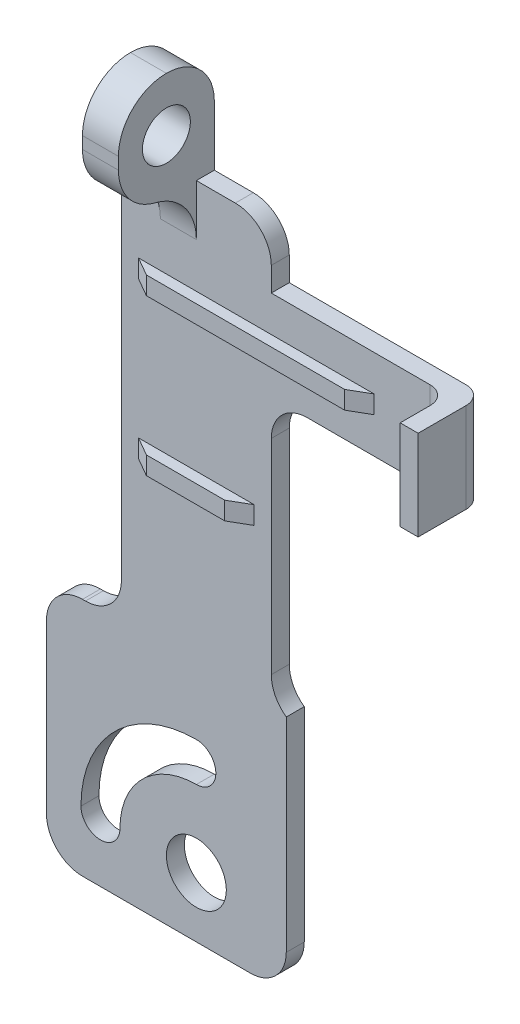
SolidWorks part; units mm, degrees
ref_plane "Front Plane" through (0, 0, 0) normal (0, 0, 1) x (1, 0, 0)
ref_plane "Top Plane" through (0, 0, 0) normal (0, 1, 0) x (1, 0, 0)
ref_plane "Right Plane" through (0, 0, 0) normal (1, 0, 0) x (0, 0, -1)
sketch "Sketch1" plane through (0, 0, 0) normal (0, 0, 1) x (1, 0, 0)
  line L1 (-12.5, 0) -> (-12.5, -70)
  line L2 (-12.5, -70) -> (-25, -70)
  line L3 (-25, -70) -> (-25, -110)
  line L4 (-25, -110) -> (15, -110)
  line L5 (15, -110) -> (15, -70)
  line L6 (15, -70) -> (12.5, -70)
  line L7 (12.5, -70) -> (12.5, -25)
  line L8 (12.5, -25) -> (45, -25)
  line L9 (45, -25) -> (45, -10)
  line L10 (12.5, -70) -> (-12.5, -70) construction
  line L12 (12.5, 0) -> (12.5, -10)
  line L13 (12.5, -10) -> (45, -10)
  line L14 (-12.5, 0) -> (0, 0)
  line L15 (0, 0) -> (12.5, 0)
  point P12 (0, -70)
  dimension "D1" = 10
  dimension "D2" = 15
  dimension "D3" = 25
  dimension "D4" = 25
  dimension "D5" = 40
  dimension "D6" = 45
  dimension "D7" = 110
  dimension "D8" = 15
extrude "Boss-Extrude1" add sketch "Sketch1" along normal blind 3
sketch "Sketch4" plane through (0, 0, 3) normal (0, 0, 1) x (1, 0, 0)
  line L1 (0, -55) -> (0, 55) construction
  circle A0 centre (0, -100) radius 5
  point P3 (0, -100)
  dimension "D1" = 10
  dimension "D2" = 100
extrude "Cut-Extrude1" cut sketch "Sketch4" against normal blind 10.4
ref_plane "Plane1" through (0, -100, 0) normal (0, 1, 0) x (1, 0, 0)
ref_axis "Axis1" through (0, -100, -80.99) along (0, 0, 1)
sketch "Sketch7" plane through (0, -100, 0) normal (0, 1, 0) x (1, 0, 0)
  line L1 (-19.25, 0) -> (-12.75, 0)
  line L2 (-19.25, 0) -> (-19.25, -3)
  line L3 (-19.25, -3) -> (-12.75, -3)
  line L4 (-12.75, 0) -> (-12.75, -3)
  line L6 (-25, 0) -> (15, 0) construction
  line L7 (0, -55) -> (0, 55) construction
  line L8 (-25, -3) -> (15, -3) construction
  point P8 (-16, -3)
  dimension "D1" = 6.5
  dimension "D2" = 16
revolve "Cut-Revolve1" cut sketch "Sketch7" angle 90 about axis through (0, -100, -80.99) along (0, 0, 1) reverse direction yes
sketch "Sketch8" plane through (0, 0, 0) normal (0, 0, 1) x (1, 0, 0)
  line L0 (-19.25, -100) -> (-12.75, -100) construction
  line L1 (0, -80.75) -> (0, -87.25) construction
  circle A0 centre (-16, -100) radius 3.25
  circle A1 centre (0, -84) radius 3.25
extrude "Cut-Extrude2" cut sketch "Sketch8" along normal through all contours A1 | A0 region at (0, -84, 0)
sketch "Sketch9" plane through (0, 0, 0) normal (1, 0, 0) x (0, 0, -1)
  line L1 (0, 18) -> (-16, 18)
  line L2 (0, 18) -> (0, 0)
  line L3 (0, 0) -> (-16, 0)
  line L4 (-16, 18) -> (-16, 0)
  dimension "D1" = 16
  dimension "D2" = 18
extrude "Boss-Extrude2" add sketch "Sketch9" against normal blind 6
sketch "Sketch10" plane through (0, 0, 0) normal (1, 0, 0) x (0, 0, -1)
  line L0 (0, 18) -> (-16, 18) construction
  line L1 (-16, 18) -> (-16, 0) construction
  circle A0 centre (-8, 9) radius 4
  point P5 (-8, 18)
  point P9 (-16, 9)
  dimension "D1" = 8
extrude "Cut-Extrude3" cut sketch "Sketch10" against normal blind 8
fillet "Fillet1" radius 8 3 edges at (-3, 0, 16) (-3, 18, 0) (-3, 18, 16)
fillet "Fillet2" radius 9 1 edges at (-3, 0, 3)
sketch "Sketch11" plane through (0, 0, 3) normal (0, 0, 1) x (1, 0, 0)
  line L0 (12.5, -25) -> (45, -25) construction
  line L1 (45, -10) -> (42, -10)
  line L2 (45, -10) -> (45, -25)
  line L3 (45, -25) -> (42, -25)
  line L4 (42, -10) -> (42, -25)
  dimension "D1" = 3
extrude "Boss-Extrude3" add sketch "Sketch11" along normal blind 8 contours L2 L1 L4 L3
fillet "Fillet3" radius 3 2 edges at (45, -17.5, 0) (42, -17.5, 3)
fillet "Fillet4" radius 6 8 edges at (-12.5, 0, 1.5) (12.5, 0, 1.5) (12.5, -25, 1.5) (15, -110, 1.5) (-25, -110, 1.5) (-12.5, -70, 1.5) (-25, -70, 1.5) (12.5, -70, 1.5)
sketch "Sketch12" plane through (0, 0, 3) normal (0, 0, 1) x (1, 0, 0)
  line L0 (39, -25) -> (39, -10) construction
  line L1 (-10, -19) -> (30, -19)
  line L2 (-10, -19) -> (-10, -16)
  line L3 (-10, -16) -> (30, -16)
  line L4 (30, -19) -> (30, -16)
  line L5 (-10, -19) -> (30, -16) construction
  line L6 (-10, -16) -> (30, -19) construction
  line L7 (-10, -45) -> (10, -45)
  line L8 (-10, -45) -> (-10, -42)
  line L9 (-10, -42) -> (10, -42)
  line L10 (10, -45) -> (10, -42)
  line L11 (-10, -45) -> (10, -42) construction
  line L12 (-10, -42) -> (10, -45) construction
  point P0 (10, -17.5)
  point P5 (0, -43.5)
  point P17 (39, -17.5)
  dimension "D1" = 3
  dimension "D2" = 20
  dimension "D3" = 40
  dimension "D4" = 26
extrude "Boss-Extrude4" add sketch "Sketch12" along normal blind 1.8
chamfer "Chamfer1" distance 2 angle 60 4 edges at (10, -43.5, 4.8) (-10, -43.5, 4.8) (-10, -17.5, 4.8) (30, -17.5, 4.8) first distance on face at (10, -43.5, 3.9) first distance on face at (-10, -43.5, 3.9) first distance on face at (-10, -17.5, 3.9) first distance on face at (30, -17.5, 3.9)
